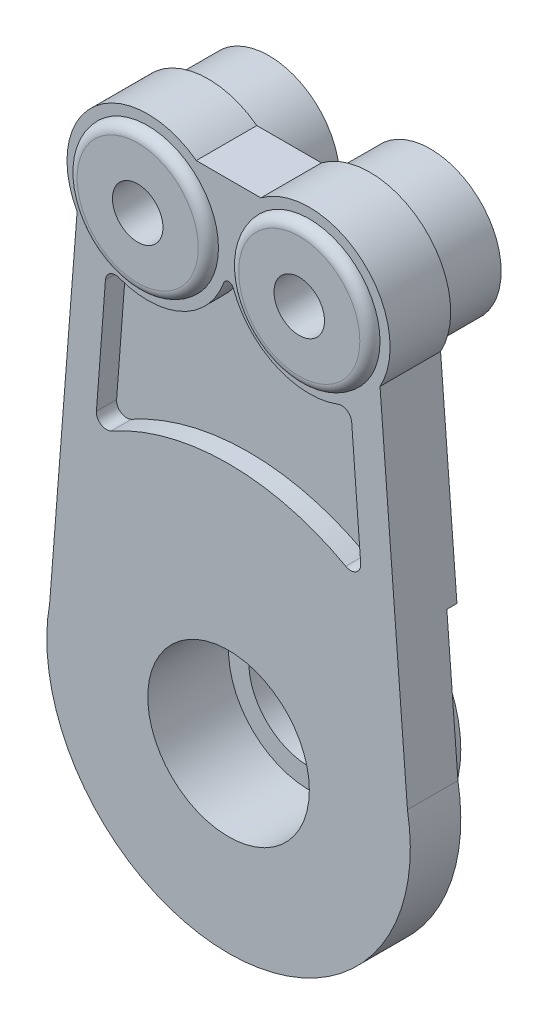
SolidWorks part; units mm, degrees
ref_plane "Plane1" through (0, 0, 0) normal (0, 0, 1) x (1, 0, 0)
ref_plane "Plane2" through (0, 0, 0) normal (0, 1, 0) x (1, 0, 0)
ref_plane "Plane3" through (0, 0, 0) normal (1, 0, 0) x (0, 0, -1)
sketch "Esquisse1" plane through (0, 0, 0) normal (0, 0, 1) x (1, 0, 0)
  line L0 (0, 0) -> (0, 54) construction
  line L1 (-8.8587, 1.5885) -> (-7.5, 19.0635)
  line L2 (1.6, 24.2) -> (-1.6, 24.2)
  line L3 (8.8587, 1.5885) -> (7.5, 19.0635)
  arc A2 (-8.8587, 1.5885) -> (8.8587, 1.5885) centre (0, 0) ccw
  arc A3 (-1.6, 24.2) -> (-7.5, 19.0635) centre (-4, 21) ccw
  arc A4 (1.6, 24.2) -> (7.5, 19.0635) centre (4, 21) cw
  dimension "D2" = 15
  dimension "D4" = 18
  dimension "D5" = 8
  dimension "D1" = 8
  dimension "D3" = 21
extrude "Base-Extrusion" add sketch "Esquisse1" along normal blind 3
sketch "Esquisse2" plane through (0, 0, 3) normal (0, 0, 1) x (1, 0, 0)
  circle A0 centre (4, 21) radius 3.5
  circle A1 centre (-4, 21) radius 3.5
  dimension "D1" = 7
  dimension "D2" = 7
extrude "Boss.-Extru.1" add sketch "Esquisse2" along normal blind 0.5
fillet "Congé1" radius 0.5
sketch "Esquisse3" plane through (0, 0, 3) normal (0, 0, 1) x (1, 0, 0)
  line L0 (-8.8587, 1.2589) -> (-7.5, 19.0635) construction
  line L1 (0, 0) -> (0, 26) construction
  line L2 (-6.5437, 10.9791) -> (-6.0971, 16.8315)
  line L3 (6.5437, 10.9791) -> (6.0971, 16.8315)
  arc A0 (5.8034, 10.5034) -> (-5.8034, 10.5034) centre (0, 0) ccw
  arc A1 (-5.4209, 17.2609) -> (-0.2353, 19.6483) centre (-4, 21) ccw
  arc A2 (0.2353, 19.6483) -> (5.4209, 17.2609) centre (4, 21) ccw
  arc A3 (-6.5437, 10.9791) -> (-5.8034, 10.5034) centre (-6.0452, 10.941) ccw
  arc A4 (6.5437, 10.9791) -> (5.8034, 10.5034) centre (6.0452, 10.941) cw
  arc A5 (5.4209, 17.2609) -> (6.0971, 16.8315) centre (5.5986, 16.7935) cw
  arc A8 (-6.0971, 16.8315) -> (-5.4209, 17.2609) centre (-5.5986, 16.7935) cw
  arc A9 (-0.2353, 19.6483) -> (0.2353, 19.6483) centre (0, 19.5639) cw
  point P31 (0, 21)
  dimension "D1" = 24
  dimension "D2" = 0.5
  dimension "D3" = 0.25
extrude "Enlèv. mat.-Extru.1" cut sketch "Esquisse3" against normal blind 1
sketch "Esquisse4" plane through (0, 0, 3.5) normal (0, 0, 1) x (1, 0, 0)
  circle A0 centre (4, 21) radius 1.25
  circle A1 centre (-4, 21) radius 1.25
  dimension "D1" = 2.5
  dimension "D2" = 2.5
sketch "Esquisse5" plane through (0, 0, 0) normal (0, 0, -1) x (-1, 0, 0)
  circle A0 centre (4, 21) radius 3.5
  circle A1 centre (-4, 21) radius 3.5
  dimension "D1" = 7
  dimension "D2" = 7
extrude "Boss.-Extru.2" add sketch "Esquisse5" along normal blind 3
extrude "Enlèv. mat.-Extru.3" cut sketch "Esquisse4" against normal through all
sketch "Esquisse7" plane through (0, 0, 0) normal (0, 0, -1) x (-1, 0, 0)
  point P0 (0, 13)
sketch "Esquisse9" plane through (0, 0, 0) normal (0, 0, -1) x (-1, 0, 0)
  circle A0 centre (0, 0) radius 12
  dimension "D1" = 24
extrude "Enlèv. mat.-Extru.4" cut sketch "Esquisse9" against normal blind 0.5
sketch "Esquisse11" plane through (0, 0, 0.5) normal (0, 0, -1) x (-1, 0, 0)
  line L0 (0, 0) -> (0, -14) construction
  line L1 (1.5, -5.8095) -> (1.5, -8.8741)
  line L2 (-1.5, -5.8095) -> (-1.5, -8.8741)
  arc A0 (-1.5, -8.8741) -> (1.5, -8.8741) centre (0, 0) ccw
  arc A1 (1.5, -5.8095) -> (-1.5, -5.8095) centre (0, 0) ccw
  dimension "D1" = 12
  dimension "D2" = 3
extrude "Boss.-Extru.3" add sketch "Esquisse11" along normal blind 3
sketch "Esquisse12" plane through (0, 0, 3) normal (0, 0, 1) x (1, 0, 0)
  circle A0 centre (0, 0) radius 4
  dimension "D1" = 8
extrude "Enlèv. mat.-Extru.5" cut sketch "Esquisse12" against normal blind 4
sketch "Esquisse13" plane through (0, 0, -1) normal (0, 0, 1) x (1, 0, 0)
  circle A0 centre (0, 0) radius 3
  dimension "D1" = 6
extrude "Enlèv. mat.-Extru.6" cut sketch "Esquisse13" against normal through all
